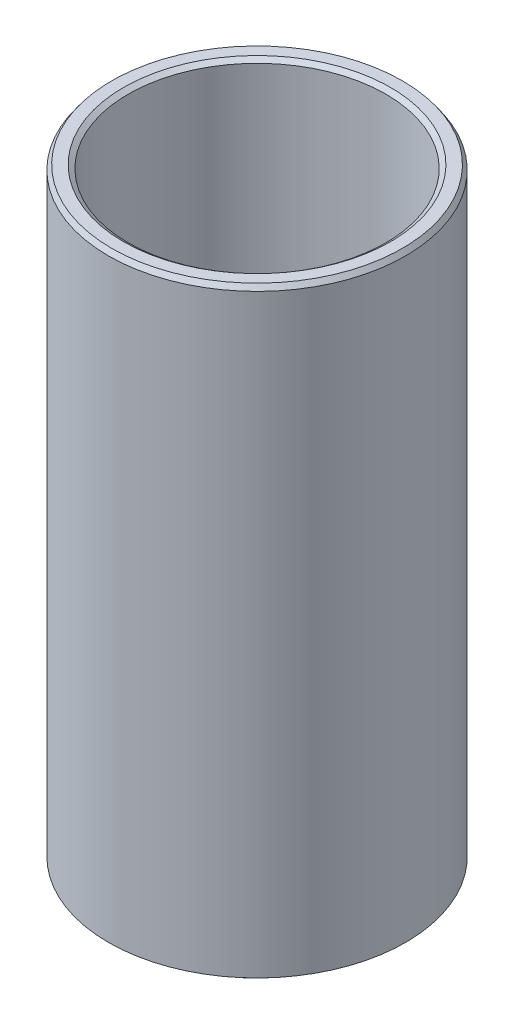
SolidWorks part; units mm, degrees
ref_plane "Front Plane" through (0, 0, 0) normal (0, 0, 1) x (1, 0, 0)
ref_plane "Top Plane" through (0, 0, 0) normal (0, 1, 0) x (1, 0, 0)
ref_plane "Right Plane" through (0, 0, 0) normal (1, 0, 0) x (0, 0, -1)
sketch "Sketch1" plane through (0, 0, 0) normal (0, 1, 0) x (1, 0, 0)
  circle A0 centre (0, 0) radius 50
  dimension "SLEEVE_OD" = 100
extrude "Boss-Extrude1" add sketch "Sketch1" along normal blind 202.7564
sketch "Sketch2" plane through (0, 0, 0) normal (0, 1, 0) x (1, 0, 0)
  circle A0 centre (0, 0) radius 43.3351
  dimension "BORE_D" = 86.6701
extrude "Cut-Extrude1" cut sketch "Sketch2" along normal through all
chamfer "Chamfer1" distance 1.6006 angle 35.413 4 edges at (0, 202.7564, 43.3351) (0, 0, 43.3351) (0, 0, 50) (0, 202.7564, 50) first distance on face at (0, 202.7564, 43.3351) first distance on face at (0, 0, 43.3351) first distance on face at (0, 202.7564, 50)
